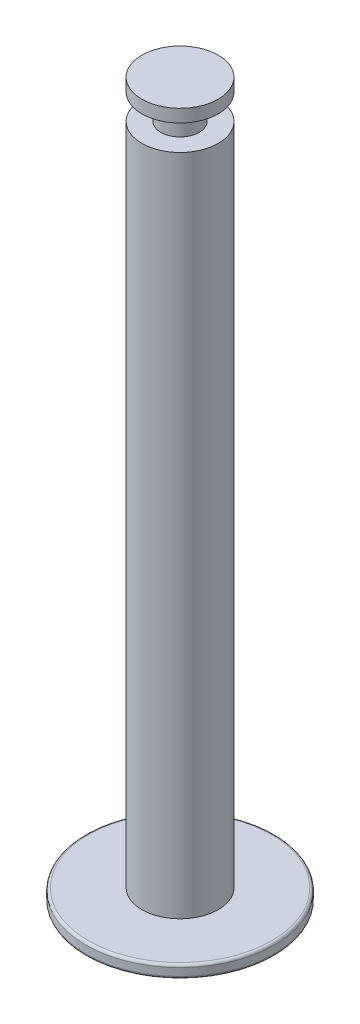
SolidWorks part; units mm, degrees
ref_plane "Front Plane" through (0, 0, 0) normal (0, 0, 1) x (1, 0, 0)
ref_plane "Top Plane" through (0, 0, 0) normal (0, 1, 0) x (1, 0, 0)
ref_plane "Right Plane" through (0, 0, 0) normal (1, 0, 0) x (0, 0, -1)
sketch "Sketch1" plane through (0, 0, 0) normal (0, 1, 0) x (1, 0, 0)
  circle A0 centre (0, 0) radius 7.39
extrude "Boss-Extrude1" add sketch "Sketch1" along normal blind 1
fillet "Fillet1" radius 0.2 2 edges at (0, 0, 7.39) (0, 1, 7.39)
sketch "Sketch2" plane through (0, 1, 0) normal (0, 1, 0) x (1, 0, 0)
  circle A0 centre (0, 0) radius 2.99
extrude "Boss-Extrude3" add sketch "Sketch2" along normal blind 52
sketch "Sketch3" plane through (0, 53, 0) normal (0, 1, 0) x (1, 0, 0)
  circle A0 centre (0, 0) radius 1.5
extrude "Boss-Extrude4" add sketch "Sketch3" along normal blind 2
sketch "Sketch4" plane through (0, 55, 0) normal (0, 1, 0) x (1, 0, 0)
  circle A0 centre (0, 0) radius 2.99
extrude "Boss-Extrude5" add sketch "Sketch4" along normal blind 1
ref_axis "Axis1" through (0, 79.4873, 0) along (0, -1, 0)
